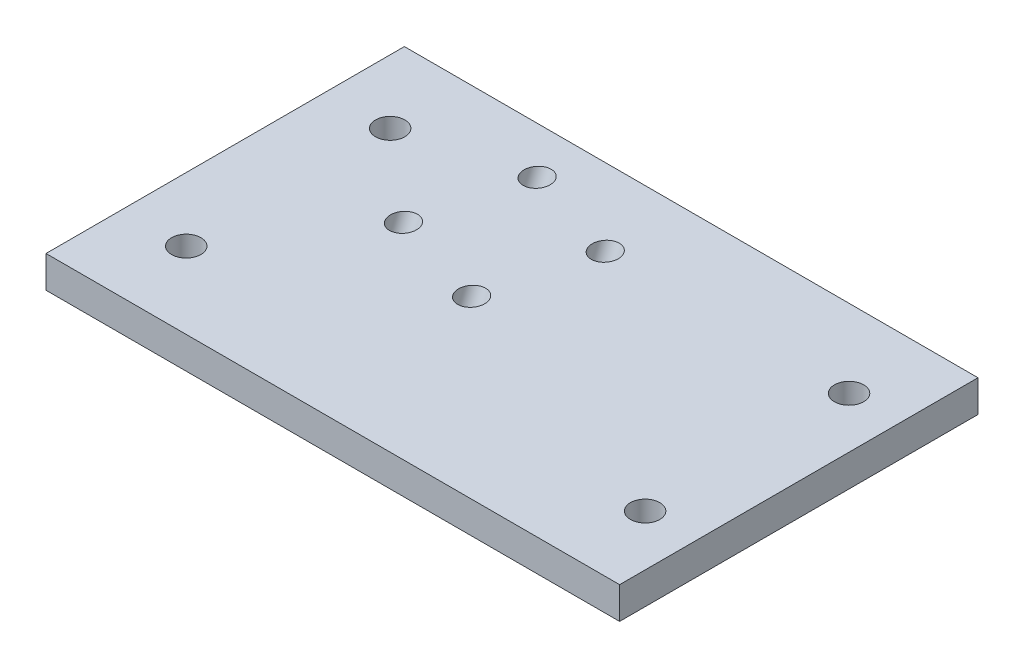
SolidWorks part; units mm, degrees
ref_plane "Front" through (0, 0, 0) normal (0, 0, 1) x (1, 0, 0)
ref_plane "Top" through (0, 0, 0) normal (0, 1, 0) x (1, 0, 0)
ref_plane "Right" through (0, 0, 0) normal (1, 0, 0) x (0, 0, -1)
sketch "Sketch1" plane through (0, 0, 0) normal (0, 1, 0) x (1, 0, 0)
  line L1 (0, 0) -> (90, 0)
  line L2 (0, 0) -> (0, 56.23)
  line L3 (0, 56.23) -> (90, 56.23)
  line L4 (90, 0) -> (90, 56.23)
  dimension "D1" = 90
  dimension "D2" = 56.23
extrude "Boss-Extrude1" add sketch "Sketch1" along normal blind 5
sketch "Sketch2" plane through (0, 5, 0) normal (0, 1, 0) x (1, 0, 0)
  circle A0 centre (82, 12) radius 2.3
  circle A1 centre (10, 12) radius 2.3
extrude "Cut-Extrude1" cut sketch "Sketch2" against normal blind 15
sketch "Sketch4" plane through (0, 5, 0) normal (0, 1, 0) x (1, 0, 0)
  circle A0 centre (39.2121, 27.5705) radius 2.2
  circle A1 centre (23.8176, 32.2728) radius 2.2
  circle A2 centre (43.572, 44.174) radius 2.2
  circle A3 centre (28.1775, 48.8763) radius 2.2
ref_plane "Plane1" through (0, 23.8287, -9.6274) normal (0, 0.9272, -0.3746) x (-1, 0, 0)
sketch "Sketch6" plane through (0, 23.8287, -9.6274) normal (0, 0.9272, -0.3746) x (-1, 0, 0)
  circle A0 centre (-28.1775, -43.4443) radius 2.0398
  circle A1 centre (-23.8176, -28.0498) radius 2.0398
  circle A2 centre (-39.2121, -23.6899) radius 2.0398
  circle A3 centre (-43.572, -39.0844) radius 2.0398
extrude "Cut-Extrude2" cut sketch "Sketch6" against normal blind 45
sketch "Sketch7" plane through (0, 5, 0) normal (0, 1, 0) x (1, 0, 0)
  circle A0 centre (82, 44) radius 2.3
  circle A1 centre (10, 44) radius 2.3
extrude "Cut-Extrude3" cut sketch "Sketch7" against normal blind 45
